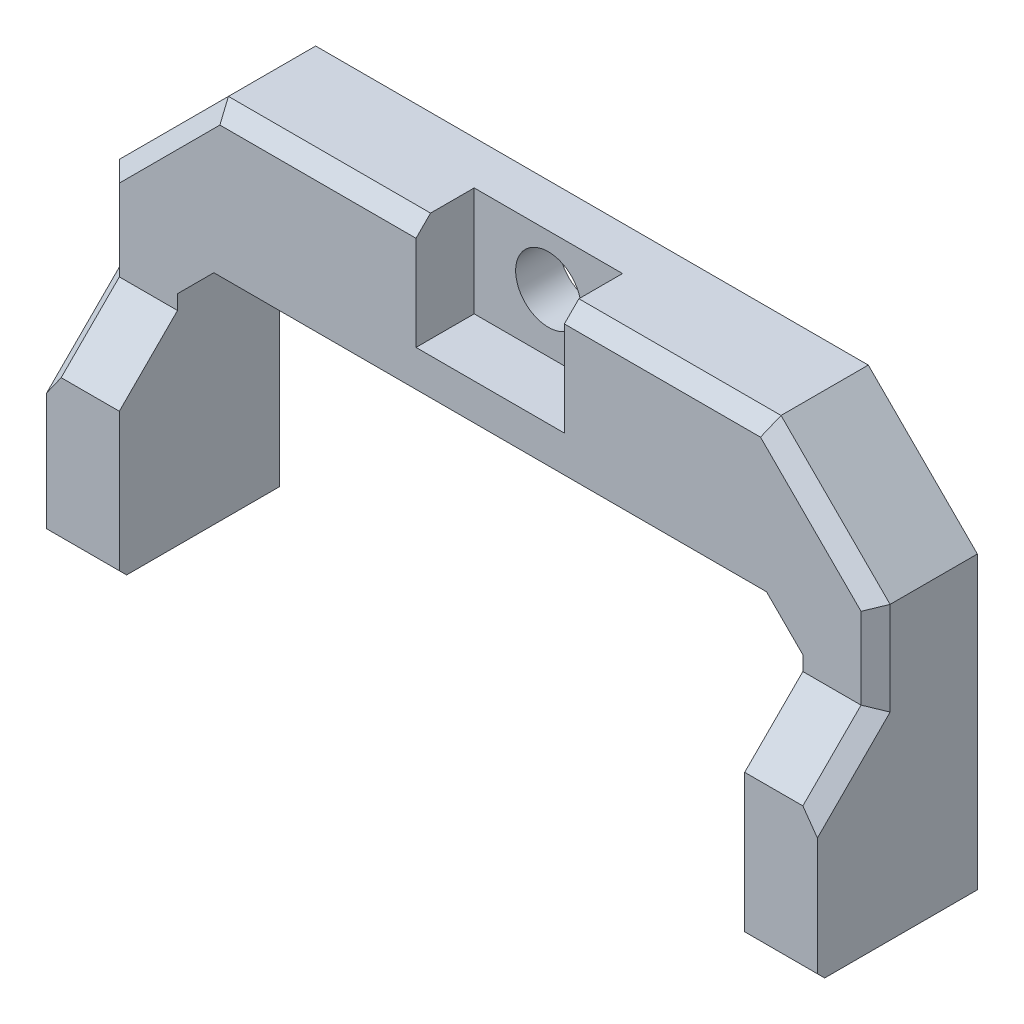
SolidWorks part; units mm, degrees
ref_plane "Front Plane" through (0, 0, 0) normal (0, 0, 1) x (1, 0, 0)
ref_plane "Top Plane" through (0, 0, 0) normal (0, 1, 0) x (1, 0, 0)
ref_plane "Right Plane" through (0, 0, 0) normal (1, 0, 0) x (0, 0, -1)
sketch "Sketch1" plane through (0, 0, 0) normal (0, 0, 1) x (1, 0, 0)
  line L0 (0, 0) -> (0, -10)
  line L1 (0, -10) -> (-19, -10)
  line L2 (-19, -10) -> (-21.5, -12.5)
  line L3 (-21.5, -12.5) -> (-21.5, -27.5)
  line L4 (-21.5, -27.5) -> (-26.5, -27.5)
  line L5 (-26.5, -27.5) -> (-26.5, -7.5)
  line L6 (-26.5, -7.5) -> (-19, 0)
  line L7 (-19, 0) -> (0, 0)
  dimension "D1" = 135
  dimension "D2" = 21.5
  dimension "D3" = 5
  dimension "D4" = 15
  dimension "D5" = 10
  dimension "D6" = 2.5
extrude "Boss-Extrude1" add sketch "Sketch1" along normal blind 7
sketch "Sketch6" plane through (0, 0, 7) normal (0, 0, 1) x (1, 0, 0)
  line L0 (-21.5, -27.5) -> (-21.5, -12.5) construction
  line L1 (-26.5, -27.5) -> (-21.5, -27.5)
  line L2 (-26.5, -27.5) -> (-26.5, -17.5)
  line L3 (-26.5, -17.5) -> (-21.5, -17.5)
  line L4 (-21.5, -27.5) -> (-21.5, -17.5)
  dimension "D1" = 10
extrude "Boss-Extrude2" add sketch "Sketch6" along normal blind 4
sketch "Sketch3" plane through (0, 0, 7) normal (0, 0, 1) x (1, 0, 0)
  line L1 (0, 0) -> (-5.1, 0)
  line L2 (0, 0) -> (0, -7.5)
  line L3 (0, -7.5) -> (-5.1, -7.5)
  line L4 (-5.1, 0) -> (-5.1, -7.5)
  dimension "D1" = 7.5
  dimension "D2" = 5.1
extrude "Cut-Extrude1" cut sketch "Sketch3" against normal blind 4
mirror "Mirror1" about plane through (0, 0, 7) normal (-1, 0, 0) of "Boss-Extrude2", "Boss-Extrude1", "Cut-Extrude1"
hole_wizard "M4 Clearance Hole1" positions "Sketch4" profile "Sketch5" hole size "M4" standard "ANSI Metric" end condition through all
sketch "Sketch4" plane through (0, 0, 3) normal (0, 0, 1) x (1, 0, 0)
  line L0 (-5.1, -7.5) -> (5.1, -7.5) construction
  line L1 (0, -3.85) -> (0, 3.85) construction
  point P0 (0, -3.5)
  dimension "D1" = 4
sketch "Sketch5" plane through (0, -3.5, 3) normal (1, 0, 0) x (0, -1, 0)
  line L0 (0, 0) -> (0, 3)
  line L1 (0, 3) -> (2.25, 3)
  line L2 (2.25, 3) -> (2.25, 0)
  line L5 (2.25, 0) -> (0, 0)
  line L11 (0, -6.35) -> (0, 107.95) construction
  dimension "Thru Hole Dia." = 4.5
  dimension "Thru Hole Depth" = 3
chamfer "Chamfer2" distance 4 2 edges at (24, -17.5, 7) (-24, -17.5, 7)
chamfer "Chamfer4" distance 1 angle 45 8 edges at (26.5, -10.5, 7) (22.75, -3.75, 7) (12.05, 0, 7) (-26.5, -10.5, 7) (-22.75, -3.75, 7) (-12.05, 0, 7) (26.5, -15.5, 9) (-26.5, -15.5, 9)
chamfer "Chamfer5" distance 0.5 angle 45 2 edges at (24, -27.5, 11) (-24, -27.5, 11)
equation "\"a\"=1"
